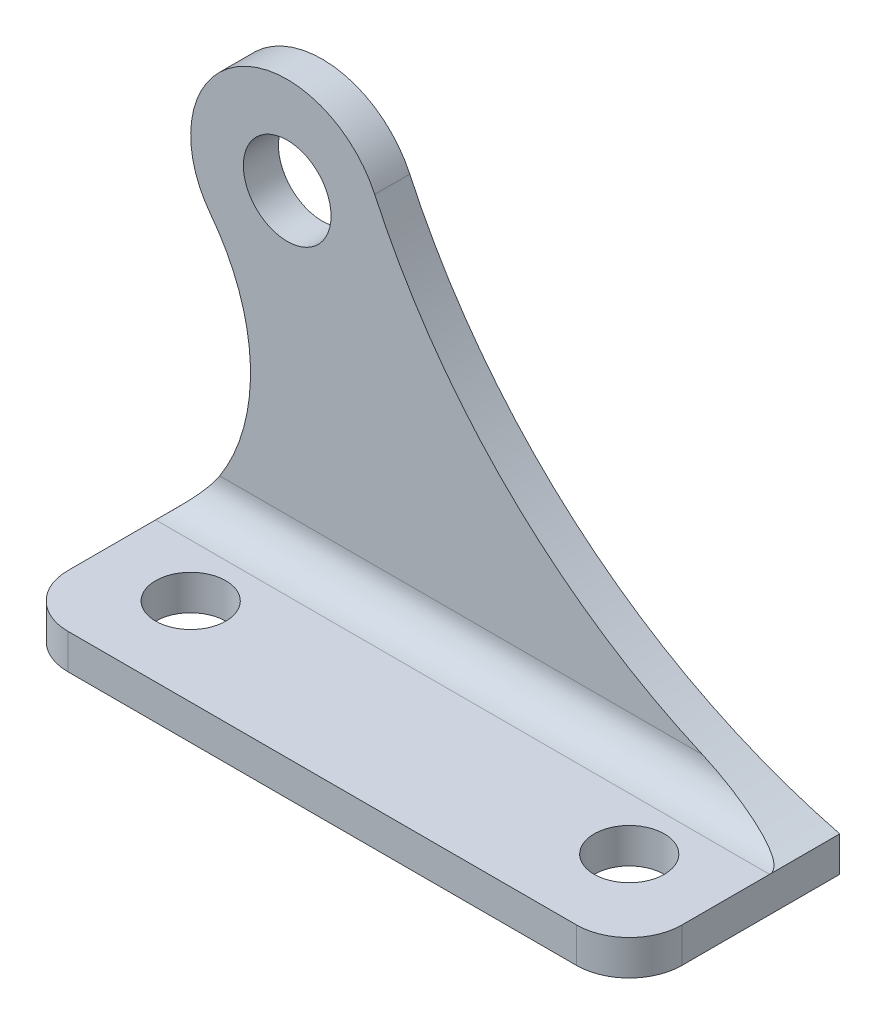
SolidWorks part; units mm, degrees
ref_plane "Front Plane" through (0, 0, 0) normal (0, 0, 1) x (1, 0, 0)
ref_plane "Top Plane" through (0, 0, 0) normal (0, 1, 0) x (1, 0, 0)
ref_plane "Right Plane" through (0, 0, 0) normal (1, 0, 0) x (0, 0, -1)
sketch "Sketch1" plane through (0, 0, 0) normal (0, 0, 1) x (1, 0, 0)
  line L0 (0, 34.5512) -> (0, -21.8179) construction
  line L1 (-25.489, 0) -> (33.3088, 0) construction
  line L2 (-5.5, 0) -> (-5.5, 2)
  line L4 (29.5, 2) -> (29.5, 0)
  line L5 (29.5, 0) -> (-5.5, 0)
  circle A0 centre (0, 20) radius 2.5
  arc A1 (4.9899, 22.3131) -> (-4.3644, 16.653) centre (0, 20) ccw
  arc A2 (4.9899, 22.3131) -> (29.5, 2) centre (38.5587, 37.874) ccw
  arc A3 (-4.3644, 16.653) -> (-5.5, 2) centre (-13.0931, 9.959) cw
  dimension "D1" = 5
  dimension "D3" = 3
  dimension "D6" = 37
  dimension "D7" = 11
  dimension "D2" = 20
  dimension "D4" = 2
  dimension "D5" = 35
extrude "Boss-Extrude1" add sketch "Sketch1" along normal blind 2
sketch "Sketch2" plane through (0, 0, 2) normal (0, 0, 1) x (1, 0, 0)
  line L1 (-5.5, 0) -> (29.5, 0)
  line L2 (-5.5, 0) -> (-5.5, 2)
  line L3 (-5.5, 2) -> (29.5, 2)
  line L4 (29.5, 0) -> (29.5, 2)
extrude "Boss-Extrude2" add sketch "Sketch2" along normal blind 10
sketch "Sketch3" plane through (0, 2, 0) normal (0, 1, 0) x (1, 0, 0)
  line L0 (-10.6996, -7) -> (35.8591, -7) construction
  line L1 (-5.5, -12) -> (-5.5, -2) construction
  line L2 (29.5, -12) -> (29.5, -2) construction
  line L3 (29.5, -12) -> (-5.5, -12) construction
  circle A0 centre (-0.5, -7) radius 2
  circle A1 centre (24.5, -7) radius 2
  dimension "D1" = 4
  dimension "D2" = 4
  dimension "D3" = 5
  dimension "D4" = 5
  dimension "D5" = 5
extrude "Cut-Extrude1" cut sketch "Sketch3" against normal through all
fillet "Fillet1" radius 2 1 edges at (12, 2, 2)
fillet "Fillet2" radius 3 2 edges at (-5.5, 1, 12) (29.5, 1, 12)
